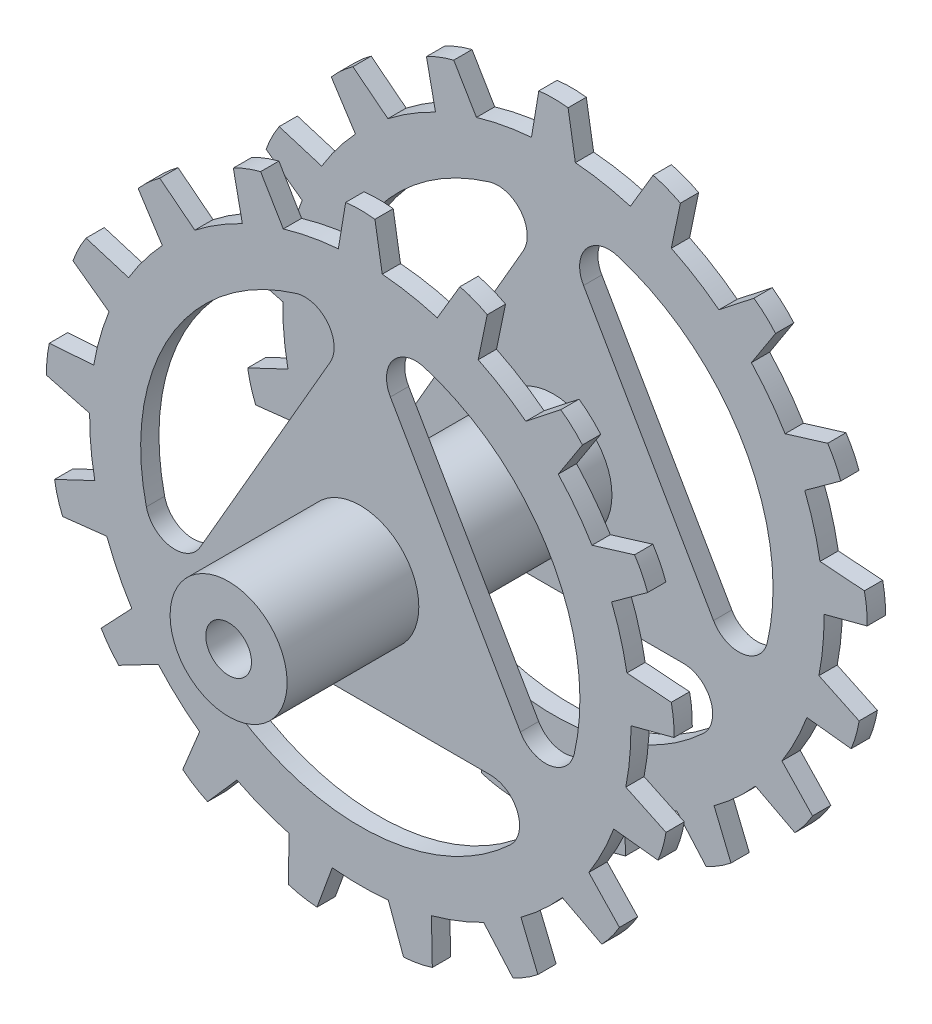
SolidWorks part; units mm, degrees
ref_plane "Front Plane" through (0, 0, 0) normal (0, 0, 1) x (1, 0, 0)
ref_plane "Top Plane" through (0, 0, 0) normal (0, 1, 0) x (1, 0, 0)
ref_plane "Right Plane" through (0, 0, 0) normal (1, 0, 0) x (0, 0, -1)
sketch "Sketch2" plane through (0, 0, 0) normal (0, 0, 1) x (1, 0, 0)
  line L0 (0, 0) -> (0, 39.2003) construction
  line L1 (-1.27, 27.2276) -> (-1.905, 23.4176)
  line L2 (1.27, 27.2276) -> (1.905, 23.4176)
  line L3 (11.02, 24.9302) -> (10.2358, 21.1481)
  line L4 (8.6515, 25.8478) -> (6.6831, 22.5245)
  line L5 (19.2817, 19.2659) -> (17.1842, 16.0225)
  line L6 (17.4046, 20.9771) -> (14.3686, 18.5892)
  line L7 (24.9393, 10.9995) -> (21.8117, 8.7329)
  line L8 (23.8071, 13.2733) -> (20.1135, 12.1434)
  line L9 (27.2287, 1.2477) -> (23.4935, 0.2638)
  line L10 (26.9943, 3.7768) -> (23.142, 4.0576)
  line L11 (25.8407, -8.6727) -> (22.0024, -8.2408)
  line L12 (26.5358, -6.2297) -> (23.045, -4.5763)
  line L13 (20.9628, -17.4218) -> (17.5397, -15.6325)
  line L14 (22.4935, -15.3948) -> (19.8357, -12.5921)
  line L15 (13.2537, -23.818) -> (10.7081, -20.9129)
  line L16 (15.4133, -22.4808) -> (13.9475, -18.9072)
  line L17 (3.7547, -26.9974) -> (2.4304, -23.369)
  line L18 (6.2514, -26.5307) -> (6.1755, -22.6689)
  line L19 (-6.2514, -26.5307) -> (-6.1755, -22.6689)
  line L20 (-3.7547, -26.9974) -> (-2.4304, -23.369)
  line L21 (-15.4133, -22.4808) -> (-13.9475, -18.9072)
  line L22 (-13.2537, -23.818) -> (-10.7081, -20.9129)
  line L23 (-22.4935, -15.3948) -> (-19.8357, -12.5921)
  line L24 (-20.9628, -17.4218) -> (-17.5397, -15.6325)
  line L25 (-26.5358, -6.2297) -> (-23.045, -4.5763)
  line L26 (-25.8407, -8.6727) -> (-22.0024, -8.2408)
  line L27 (-26.9943, 3.7768) -> (-23.142, 4.0576)
  line L28 (-27.2287, 1.2477) -> (-23.4935, 0.2638)
  line L29 (-23.8071, 13.2733) -> (-20.1135, 12.1434)
  line L30 (-24.9393, 10.9995) -> (-21.8117, 8.7329)
  line L31 (-17.4046, 20.9771) -> (-14.3686, 18.5892)
  line L32 (-19.2817, 19.2659) -> (-17.1842, 16.0225)
  line L33 (-8.6515, 25.8478) -> (-6.6831, 22.5245)
  line L34 (-11.02, 24.9302) -> (-10.2358, 21.1481)
  line L35 (0, 19.0641) -> (-16.51, -9.5321) construction
  line L36 (-16.51, -9.5321) -> (16.51, -9.5321) construction
  line L37 (16.51, -9.5321) -> (0, 19.0641) construction
  line L38 (0, 0) -> (0, 19.0641) construction
  line L39 (0, 0) -> (16.51, -9.5321) construction
  line L40 (0, 0) -> (-16.51, -9.5321) construction
  line L41 (0, 0) -> (0, 19.0641) construction
  line L42 (-2.6134, 14.5376) -> (-13.8966, -5.0056)
  line L43 (13.8966, -5.0056) -> (2.6134, 14.5376)
  line L44 (-11.2832, -9.5321) -> (11.2832, -9.5321)
  arc A0 (-1.27, 27.2276) -> (1.27, 27.2276) centre (0, 16.8413) cw
  arc A1 (-18.5706, -4.3098) -> (-5.5529, 18.2375) centre (0, 0) cw
  arc A4 (8.6515, 25.8478) -> (11.02, 24.9302) centre (6.0838, 15.704) cw
  arc A6 (17.4046, 20.9771) -> (19.2817, 19.2659) centre (11.3459, 12.4459) cw
  arc A8 (23.8071, 13.2733) -> (24.9393, 10.9995) centre (15.0757, 7.5068) cw
  arc A10 (26.9943, 3.7768) -> (27.2287, 1.2477) centre (16.7694, 1.5539) cw
  arc A12 (26.5358, -6.2297) -> (25.8407, -8.6727) centre (16.1984, -4.6088) cw
  arc A14 (22.4935, -15.3948) -> (20.9628, -17.4218) centre (13.4396, -10.1491) cw
  arc A16 (15.4133, -22.4808) -> (13.2537, -23.818) centre (8.8658, -14.3188) cw
  arc A18 (6.2514, -26.5307) -> (3.7547, -26.9974) centre (3.0946, -16.5545) cw
  arc A20 (-3.7547, -26.9974) -> (-6.2514, -26.5307) centre (-3.0946, -16.5545) cw
  arc A22 (-13.2537, -23.818) -> (-15.4133, -22.4808) centre (-8.8658, -14.3188) cw
  arc A24 (-20.9628, -17.4218) -> (-22.4935, -15.3948) centre (-13.4396, -10.1491) cw
  arc A26 (-25.8407, -8.6727) -> (-26.5358, -6.2297) centre (-16.1984, -4.6088) cw
  arc A28 (-27.2287, 1.2477) -> (-26.9943, 3.7768) centre (-16.7694, 1.5539) cw
  arc A30 (-24.9393, 10.9995) -> (-23.8071, 13.2733) centre (-15.0757, 7.5068) cw
  arc A32 (-19.2817, 19.2659) -> (-17.4046, 20.9771) centre (-11.3459, 12.4459) cw
  arc A34 (-11.02, 24.9302) -> (-8.6515, 25.8478) centre (-6.0838, 15.704) cw
  circle A37 centre (0, 0) radius 23.495 construction
  arc A38 (-10.2358, 21.1481) -> (-14.3686, 18.5892) centre (0, 0) ccw
  arc A39 (-1.905, 23.4176) -> (-6.6831, 22.5245) centre (0, 0) ccw
  arc A40 (6.6831, 22.5245) -> (1.905, 23.4176) centre (0, 0) ccw
  arc A41 (14.3686, 18.5892) -> (10.2358, 21.1481) centre (0, 0) ccw
  arc A42 (20.1135, 12.1434) -> (17.1842, 16.0225) centre (0, 0) ccw
  arc A43 (23.142, 4.0576) -> (21.8117, 8.7329) centre (0, 0) ccw
  arc A44 (23.045, -4.5763) -> (23.4935, 0.2638) centre (0, 0) ccw
  arc A45 (19.8357, -12.5921) -> (22.0024, -8.2408) centre (0, 0) ccw
  arc A46 (13.9475, -18.9072) -> (17.5397, -15.6325) centre (0, 0) ccw
  arc A47 (6.1755, -22.6689) -> (10.7081, -20.9129) centre (0, 0) ccw
  arc A48 (-2.4304, -23.369) -> (2.4304, -23.369) centre (0, 0) ccw
  arc A49 (-10.7081, -20.9129) -> (-6.1755, -22.6689) centre (0, 0) ccw
  arc A50 (-17.5397, -15.6325) -> (-13.9475, -18.9072) centre (0, 0) ccw
  arc A51 (-22.0024, -8.2408) -> (-19.8357, -12.5921) centre (0, 0) ccw
  arc A52 (-23.4935, 0.2638) -> (-23.045, -4.5763) centre (0, 0) ccw
  arc A53 (-21.8117, 8.7329) -> (-23.142, 4.0576) centre (0, 0) ccw
  arc A54 (-17.1842, 16.0225) -> (-20.1135, 12.1434) centre (0, 0) ccw
  arc A56 (-2.6134, 14.5376) -> (-5.5529, 18.2375) centre (-4.8131, 15.8076) ccw
  arc A57 (-13.8966, -5.0056) -> (-18.5706, -4.3098) centre (-16.0963, -3.7356) cw
  arc A58 (2.6134, 14.5376) -> (5.5529, 18.2375) centre (4.8131, 15.8076) cw
  arc A59 (5.5529, 18.2375) -> (18.5706, -4.3098) centre (0, 0) cw
  arc A60 (13.8966, -5.0056) -> (18.5706, -4.3098) centre (16.0963, -3.7356) ccw
  arc A61 (11.2832, -9.5321) -> (13.0176, -13.9277) centre (11.2832, -12.0721) cw
  arc A62 (13.0176, -13.9277) -> (-13.0176, -13.9277) centre (0, 0) cw
  arc A63 (-11.2832, -9.5321) -> (-13.0176, -13.9277) centre (-11.2832, -12.0721) ccw
  circle A64 centre (0, 0) radius 5.08
  point P5 (0, 23.495)
  point P25 (0, 27.305)
  point P79 (0, 0)
  point P96 (0, 0)
  point P104 (0, 0)
  point P118 (0, 0)
  point P136 (0, 0)
  dimension "D1" = 2.54
  dimension "D8" = 10.4637
  dimension "D9" = 46.99
  dimension "D11" = 2.54
  dimension "D13" = 10.16
  dimension "D2" = 3.81
  dimension "D3" = 3.81
  dimension "D4" = 3.81
  dimension "D7" = 23.495
  dimension "D10" = 33.02
  dimension "D5" = 17
  dimension "D6" = 17
  dimension "D12" = 3
extrude "Boss-Extrude2" add sketch "Sketch2" along normal blind 1.5875 from offset 8.382
extrude "Boss-Extrude3" add sketch "Sketch2<3>" along normal blind 1.5875 from offset 8.382 separate body offset against normal yes
sketch "Sketch2<3>" plane through (0, 0, 0) normal (0, 0, 1) x (1, 0, 0) same geometry as "Sketch2"
sketch "Sketch3" plane through (0, 0, -8.382) normal (0, 0, -1) x (-1, 0, 0)
  circle A0 centre (0, 0) radius 5.08
extrude "Boss-Extrude4" add sketch "Sketch3" against normal offset from surface (29.7815 mm away) 11.43 up to face at (11.0149, 6.3595, 9.9695) offset beyond the face yes
sketch "Sketch4" plane through (0, 0, 21.3995) normal (0, 0, 1) x (1, 0, 0)
  circle A0 centre (0, 0) radius 1.9844
  dimension "D1" = 3.9688
extrude "Cut-Extrude2" cut sketch "Sketch4" against normal through all
